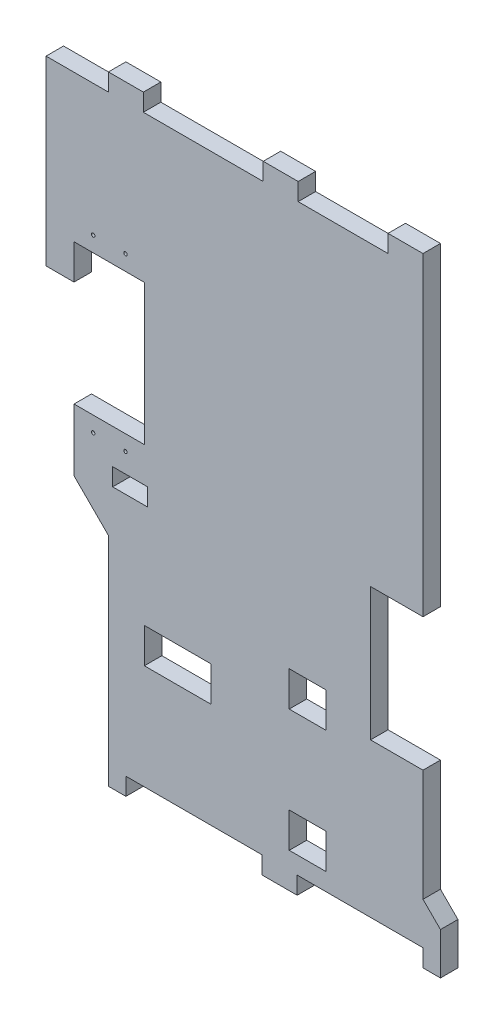
SolidWorks part; units mm, degrees
material "Balsa"
ref_plane "Plan de face" through (0, 0, 0) normal (0, 0, 1) x (1, 0, 0)
ref_plane "Plan de dessus" through (0, 0, 0) normal (0, 1, 0) x (1, 0, 0)
ref_plane "Plan de droite" through (0, 0, 0) normal (1, 0, 0) x (0, 0, -1)
sketch "Esquisse1" plane through (0, 0, 0) normal (0, 0, 1) x (1, 0, 0)
  line L0 (90, 82) -> (90, 167)
  line L1 (5, 0) -> (90, 0)
  line L2 (0, 0) -> (0, 167)
  line L3 (10, 167) -> (80, 167)
  line L4 (90, 0) -> (90, 44)
  line L5 (90, 82) -> (75, 82)
  line L6 (0, 167) -> (0, 172)
  line L7 (0, 172) -> (10, 172)
  line L8 (10, 167) -> (10, 172)
  line L9 (0, 0) -> (0, -5)
  line L10 (90, 167) -> (90, 172)
  line L11 (90, 172) -> (80, 172)
  line L12 (80, 167) -> (80, 172)
  line L13 (0, -5) -> (5, -5)
  line L14 (5, 0) -> (5, -5)
  line L16 (90, 44) -> (75, 44)
  line L17 (75, 82) -> (75, 44)
  line L18 (51.7344, 50) -> (62.2003, 50)
  line L19 (51.7344, 50) -> (51.7344, 40)
  line L20 (51.7344, 40) -> (62.2003, 40)
  line L25 (62.2003, 50) -> (62.2003, 40)
  line L32 (51.7344, 15) -> (62.2003, 15)
  line L34 (51.7344, 15) -> (51.7344, 5)
  line L35 (51.7344, 5) -> (62.2003, 5)
  line L37 (62.2003, 15) -> (62.2003, 5)
  line L54 (29.3073, 40) -> (10.2917, 40)
  line L55 (29.3073, 40) -> (29.3073, 30)
  line L56 (29.3073, 30) -> (10.2917, 30)
  line L57 (10.2917, 40) -> (10.2917, 30)
  dimension "D1" = 167
  dimension "D2" = 90
  dimension "D3" = 10
  dimension "D4" = 5
  dimension "D5" = 5
  dimension "D6" = 15
  dimension "D7" = 38
  dimension "D8" = 82
extrude "Boss.-Extru.1" add sketch "Esquisse1" along normal blind 5
sketch "Esquisse2" plane through (0, 0, 5) normal (0, 0, 1) x (1, 0, 0)
  line L0 (0, 172) -> (0, -5) construction
  line L1 (0, 167) -> (-9.8347, 167)
  line L2 (0, 167) -> (0, 57.1653)
  line L3 (0, 57.1653) -> (-9.8347, 67)
  line L4 (-9.8347, 167) -> (-9.8347, 67)
  line L6 (80, 167) -> (10, 167) construction
  dimension "D1" = 9.8347
  dimension "D2" = 135
  dimension "D3" = 100
extrude "Boss.-Extru.2" add sketch "Esquisse2" against normal blind 5
sketch "Esquisse3" plane through (0, 0, 0) normal (0, 0, -1) x (-1, 0, 0)
  line L0 (9.8347, 167) -> (9.8347, 67) construction
  line L1 (-10.3653, 125) -> (9.8347, 125)
  line L2 (-10.3653, 125) -> (-10.3653, 84.8)
  line L3 (-10.3653, 84.8) -> (9.8347, 84.8)
  line L4 (9.8347, 125) -> (9.8347, 84.8)
  line L5 (0, 167) -> (9.8347, 167) construction
  line L6 (4.3597, 129.4) -> (-4.8903, 129.4) construction
  line L7 (-4.8903, 129.4) -> (-4.8903, 80.4) construction
  line L8 (-4.8903, 80.4) -> (4.3597, 80.4) construction
  line L9 (9.8347, 167) -> (9.8347, 67) construction
  line L10 (-80, 167) -> (-10, 167) construction
  circle A0 centre (4.3597, 129.4) radius 0.5
  circle A1 centre (-4.8903, 129.4) radius 0.5
  circle A2 centre (4.3597, 80.4) radius 0.5
  circle A3 centre (-4.8903, 80.4) radius 0.5
  dimension "D9" = 1
  dimension "D1" = 17.8
  dimension "D2" = 42
  dimension "D3" = 20.2
  dimension "D4" = 9.25
  dimension "D5" = 9.25
  dimension "D6" = 49
  dimension "D7" = 14.725
  dimension "D8" = 37.6
extrude "Enlèv. mat.-Extru.1" cut sketch "Esquisse3" against normal blind 5
sketch "Esquisse4" plane through (0, 0, 5) normal (0, 0, 1) x (1, 0, 0)
  line L0 (-9.8347, 167) -> (-17.8347, 167)
  line L1 (-9.8347, 167) -> (-9.8347, 125) construction
  line L2 (-17.8347, 167) -> (-17.8347, 115)
  line L3 (-17.8347, 115) -> (-9.8347, 115)
  line L4 (-9.8347, 115) -> (-9.8347, 125)
  line L5 (-9.8347, 125) -> (-9.8347, 167)
  line L6 (0, 167) -> (-9.8347, 167) construction
  line L7 (5, 0) -> (90, 0) construction
  line L8 (44, 0) -> (54, 0)
  line L9 (44, 0) -> (44, -5)
  line L10 (44, -5) -> (54, -5)
  line L11 (54, 0) -> (54, -5)
  line L12 (0, 57.1653) -> (0, -5) construction
  line L13 (90, 0) -> (90, 44) construction
  line L14 (90, 12) -> (95, 7)
  line L15 (90, 12) -> (90, -5)
  line L16 (90, -5) -> (95, -5)
  line L17 (95, 7) -> (95, -5)
  line L18 (80, 167) -> (10, 167) construction
  line L19 (44.2889, 167) -> (54.2889, 167)
  line L20 (44.2889, 167) -> (44.2889, 172)
  line L21 (44.2889, 172) -> (54.2889, 172)
  line L22 (54.2889, 167) -> (54.2889, 172)
  line L23 (90, 82) -> (90, 172) construction
  dimension "D1" = 10
  dimension "D2" = 8
  dimension "D3" = 10
  dimension "D4" = 5
  dimension "D5" = 44
  dimension "D6" = 5
  dimension "D7" = 12
  dimension "D8" = 135
  dimension "D9" = 5
  dimension "D10" = 10
  dimension "D11" = 35.7111
extrude "Boss.-Extru.3" add sketch "Esquisse4" against normal blind 5
sketch "Esquisse5" plane through (0, 0, 5) normal (0, 0, 1) x (1, 0, 0)
  line L0 (11.2203, 74.8) -> (1.2203, 74.8)
  line L1 (11.2203, 74.8) -> (11.2203, 69.797)
  line L2 (1.2203, 74.8) -> (1.2203, 69.797)
  line L3 (11.2203, 69.797) -> (1.2203, 69.797)
  line L4 (95, -5) -> (95, 7) construction
  line L5 (90, -5) -> (95, -5) construction
  dimension "D1" = 83.7797
  dimension "D2" = 93.7797
  dimension "D3" = 12
  dimension "D4" = 74.797
  dimension "D5" = 79.8
extrude "Enlèv. mat.-Extru.2" cut sketch "Esquisse5" against normal blind 10
